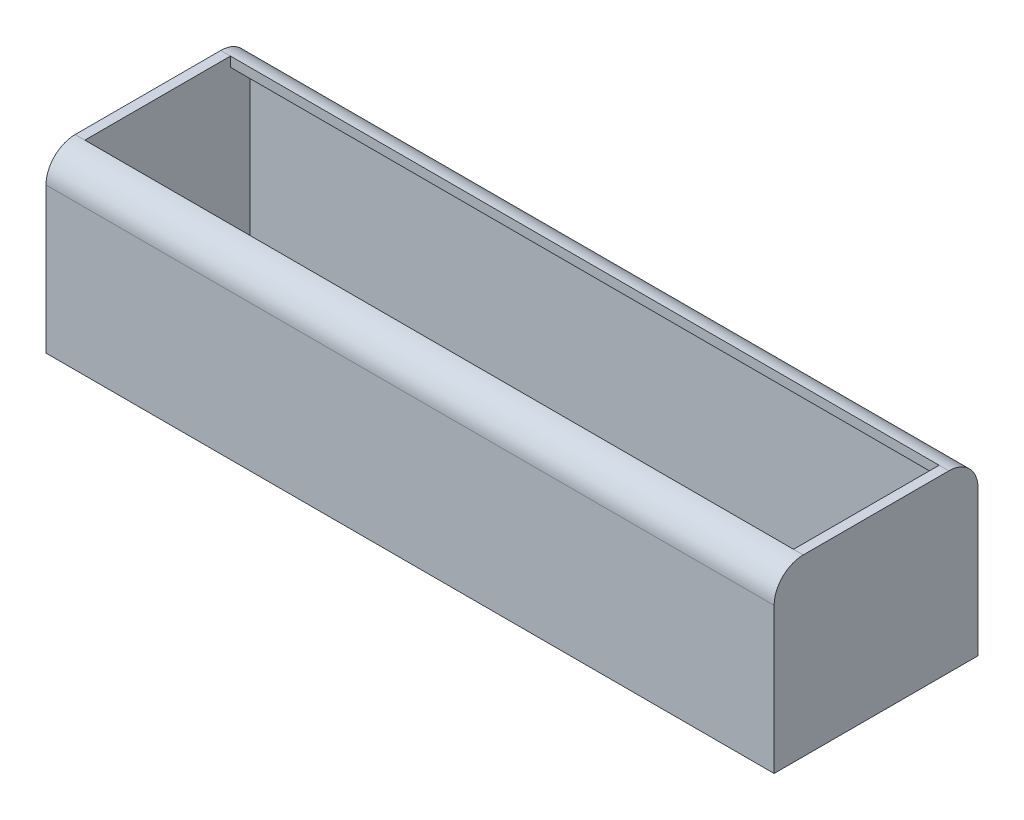
SolidWorks part; units mm, degrees
ref_plane "Front Plane" through (0, 0, 0) normal (0, 0, 1) x (1, 0, 0)
ref_plane "Top Plane" through (0, 0, 0) normal (0, 1, 0) x (1, 0, 0)
ref_plane "Right Plane" through (0, 0, 0) normal (1, 0, 0) x (0, 0, -1)
sketch "Sketch2" plane through (0, 0, 0) normal (1, 0, 0) x (0, 0, -1)
  line L1 (-10.5, -9) -> (10.5, -9)
  line L2 (-10.5, -9) -> (-10.5, 6)
  line L3 (-7.5, 9) -> (7.5, 9)
  line L4 (10.5, -9) -> (10.5, 6)
  line L5 (-10.5, -9) -> (10.5, 9) construction
  line L6 (-10.5, 9) -> (10.5, -9) construction
  arc A0 (7.5, 9) -> (10.5, 6) centre (7.5, 6) cw
  arc A1 (-10.5, 6) -> (-7.5, 9) centre (-7.5, 6) cw
  point P0 (0, 0)
  dimension "D3" = 3
  dimension "D1" = 21
  dimension "D2" = 18
extrude "Boss-Extrude1" add sketch "Sketch2" along normal blind 75
shell "Shell1" thickness 1 removed face at (37.5, 9, 0)
